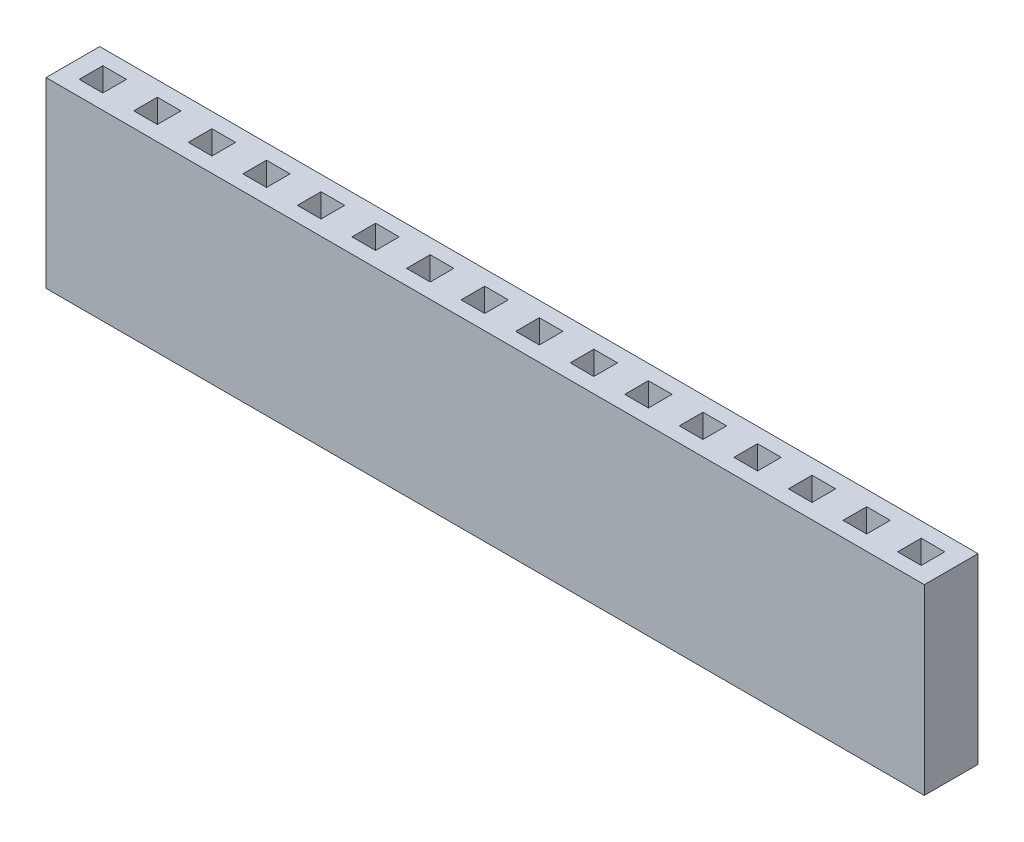
SolidWorks part; units mm, degrees
ref_plane "Front Plane" through (0, 0, 0) normal (0, 0, 1) x (1, 0, 0)
ref_plane "Top Plane" through (0, 0, 0) normal (0, 1, 0) x (1, 0, 0)
ref_plane "Right Plane" through (0, 0, 0) normal (1, 0, 0) x (0, 0, -1)
sketch "Sketch1" plane through (0, 0, 0) normal (0, 0, 1) x (1, 0, 0)
  line L1 (0, 0) -> (40.89, 0)
  line L2 (0, 0) -> (0, 8.5)
  line L3 (0, 8.5) -> (40.89, 8.5)
  line L4 (40.89, 0) -> (40.89, 8.5)
  dimension "D1" = 8.5
  dimension "D2" = 40.89
extrude "Boss-Extrude1" add sketch "Sketch1" along normal mid plane 2.5
sketch "Sketch2" plane through (0, 0, 0) normal (0, -1, 0) x (1, 0, 0)
  line L0 (0, 0) -> (40.89, 0) construction
  line L1 (40.89, 1.25) -> (40.89, -1.25) construction
  line L2 (3.385, -0.55) -> (4.485, -0.55)
  line L3 (0.845, -0.55) -> (1.945, -0.55)
  line L4 (0.845, -0.55) -> (0.845, 0.55)
  line L5 (0.845, 0.55) -> (1.945, 0.55)
  line L6 (1.945, -0.55) -> (1.945, 0.55)
  line L7 (0.845, -0.55) -> (1.945, 0.55) construction
  line L8 (0.845, 0.55) -> (1.945, -0.55) construction
  line L9 (3.385, -0.55) -> (3.385, 0.55)
  line L10 (3.385, 0.55) -> (4.485, 0.55)
  line L11 (4.485, -0.55) -> (4.485, 0.55)
  line L12 (3.385, -0.55) -> (4.485, 0.55) construction
  line L13 (3.385, 0.55) -> (4.485, -0.55) construction
  line L14 (5.925, -0.55) -> (7.025, -0.55)
  line L15 (5.925, -0.55) -> (5.925, 0.55)
  line L16 (5.925, 0.55) -> (7.025, 0.55)
  line L17 (7.025, -0.55) -> (7.025, 0.55)
  line L18 (5.925, -0.55) -> (7.025, 0.55) construction
  line L19 (5.925, 0.55) -> (7.025, -0.55) construction
  line L20 (8.465, -0.55) -> (9.565, -0.55)
  line L21 (8.465, -0.55) -> (8.465, 0.55)
  line L22 (8.465, 0.55) -> (9.565, 0.55)
  line L23 (9.565, -0.55) -> (9.565, 0.55)
  line L24 (8.465, -0.55) -> (9.565, 0.55) construction
  line L25 (8.465, 0.55) -> (9.565, -0.55) construction
  line L26 (11.005, -0.55) -> (12.105, -0.55)
  line L27 (11.005, -0.55) -> (11.005, 0.55)
  line L28 (11.005, 0.55) -> (12.105, 0.55)
  line L29 (12.105, -0.55) -> (12.105, 0.55)
  line L30 (11.005, -0.55) -> (12.105, 0.55) construction
  line L31 (11.005, 0.55) -> (12.105, -0.55) construction
  line L32 (13.545, -0.55) -> (14.645, -0.55)
  line L33 (13.545, -0.55) -> (13.545, 0.55)
  line L34 (13.545, 0.55) -> (14.645, 0.55)
  line L35 (14.645, -0.55) -> (14.645, 0.55)
  line L36 (13.545, -0.55) -> (14.645, 0.55) construction
  line L37 (13.545, 0.55) -> (14.645, -0.55) construction
  line L38 (16.085, -0.55) -> (17.185, -0.55)
  line L39 (16.085, -0.55) -> (16.085, 0.55)
  line L40 (16.085, 0.55) -> (17.185, 0.55)
  line L41 (17.185, -0.55) -> (17.185, 0.55)
  line L42 (16.085, -0.55) -> (17.185, 0.55) construction
  line L43 (16.085, 0.55) -> (17.185, -0.55) construction
  line L44 (18.625, -0.55) -> (19.725, -0.55)
  line L45 (18.625, -0.55) -> (18.625, 0.55)
  line L46 (18.625, 0.55) -> (19.725, 0.55)
  line L47 (19.725, -0.55) -> (19.725, 0.55)
  line L48 (18.625, -0.55) -> (19.725, 0.55) construction
  line L49 (18.625, 0.55) -> (19.725, -0.55) construction
  line L50 (21.165, -0.55) -> (22.265, -0.55)
  line L51 (21.165, -0.55) -> (21.165, 0.55)
  line L52 (21.165, 0.55) -> (22.265, 0.55)
  line L53 (22.265, -0.55) -> (22.265, 0.55)
  line L54 (21.165, -0.55) -> (22.265, 0.55) construction
  line L55 (21.165, 0.55) -> (22.265, -0.55) construction
  line L56 (23.705, -0.55) -> (24.805, -0.55)
  line L57 (23.705, -0.55) -> (23.705, 0.55)
  line L58 (23.705, 0.55) -> (24.805, 0.55)
  line L59 (24.805, -0.55) -> (24.805, 0.55)
  line L60 (23.705, -0.55) -> (24.805, 0.55) construction
  line L61 (23.705, 0.55) -> (24.805, -0.55) construction
  line L62 (26.245, -0.55) -> (27.345, -0.55)
  line L63 (26.245, -0.55) -> (26.245, 0.55)
  line L64 (26.245, 0.55) -> (27.345, 0.55)
  line L65 (27.345, -0.55) -> (27.345, 0.55)
  line L66 (26.245, -0.55) -> (27.345, 0.55) construction
  line L67 (26.245, 0.55) -> (27.345, -0.55) construction
  line L68 (28.785, -0.55) -> (29.885, -0.55)
  line L69 (28.785, -0.55) -> (28.785, 0.55)
  line L70 (28.785, 0.55) -> (29.885, 0.55)
  line L71 (29.885, -0.55) -> (29.885, 0.55)
  line L72 (28.785, -0.55) -> (29.885, 0.55) construction
  line L73 (28.785, 0.55) -> (29.885, -0.55) construction
  line L74 (31.325, -0.55) -> (32.425, -0.55)
  line L75 (31.325, -0.55) -> (31.325, 0.55)
  line L76 (31.325, 0.55) -> (32.425, 0.55)
  line L77 (32.425, -0.55) -> (32.425, 0.55)
  line L78 (31.325, -0.55) -> (32.425, 0.55) construction
  line L79 (31.325, 0.55) -> (32.425, -0.55) construction
  line L80 (33.865, -0.55) -> (34.965, -0.55)
  line L81 (33.865, -0.55) -> (33.865, 0.55)
  line L82 (33.865, 0.55) -> (34.965, 0.55)
  line L83 (34.965, -0.55) -> (34.965, 0.55)
  line L84 (33.865, -0.55) -> (34.965, 0.55) construction
  line L85 (33.865, 0.55) -> (34.965, -0.55) construction
  line L86 (36.405, -0.55) -> (37.505, -0.55)
  line L87 (36.405, -0.55) -> (36.405, 0.55)
  line L88 (36.405, 0.55) -> (37.505, 0.55)
  line L89 (37.505, -0.55) -> (37.505, 0.55)
  line L90 (36.405, -0.55) -> (37.505, 0.55) construction
  line L91 (36.405, 0.55) -> (37.505, -0.55) construction
  line L92 (38.945, -0.55) -> (40.045, -0.55)
  line L93 (38.945, -0.55) -> (38.945, 0.55)
  line L94 (38.945, 0.55) -> (40.045, 0.55)
  line L95 (40.045, -0.55) -> (40.045, 0.55)
  line L96 (38.945, -0.55) -> (40.045, 0.55) construction
  line L97 (38.945, 0.55) -> (40.045, -0.55) construction
  point P5 (1.395, 0)
  point P12 (3.935, 0)
  point P17 (6.475, 0)
  point P22 (9.015, 0)
  point P27 (11.555, 0)
  point P32 (14.095, 0)
  point P37 (16.635, 0)
  point P42 (19.175, 0)
  point P47 (21.715, 0)
  point P52 (24.255, 0)
  point P57 (26.795, 0)
  point P62 (29.335, 0)
  point P67 (31.875, 0)
  point P72 (34.415, 0)
  point P77 (36.955, 0)
  point P82 (39.495, 0)
  dimension "D1" = 1.1
  dimension "D3" = 1.395
  dimension "D2" = 16
extrude "Cut-Extrude1" cut sketch "Sketch2" against normal through all
ref_axis "Axis1" through (1.395, 0, 0) along (0, -1, 0)
ref_axis "Axis2" through (39.495, 0, 0) along (0, -1, 0)
